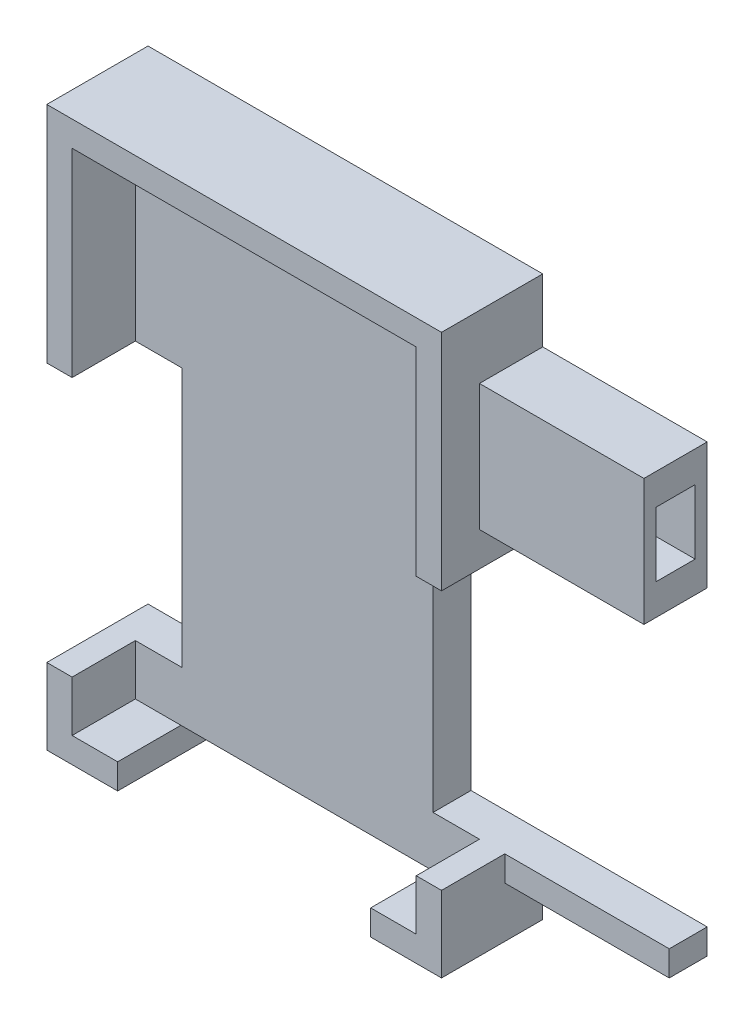
SolidWorks part; units mm, degrees
ref_plane "Front Plane" through (0, 0, 0) normal (0, 0, 1) x (1, 0, 0)
ref_plane "Top Plane" through (0, 0, 0) normal (0, 1, 0) x (1, 0, 0)
ref_plane "Right Plane" through (0, 0, 0) normal (1, 0, 0) x (0, 0, -1)
sketch "Sketch1" plane through (0, 0, 0) normal (0, 0, 1) x (1, 0, 0)
  line L0 (0, 125.6426) -> (0, -121.4419) construction
  line L1 (115.8733, 0) -> (-115.4548, 0) construction
  line L2 (15.6, 17.1) -> (28.6, 17.1)
  line L3 (-13.6, 20.1) -> (13.6, 20.1)
  line L4 (-13.6, 20.1) -> (-13.6, -20.1)
  line L5 (-13.6, -20.1) -> (13.6, -20.1)
  line L6 (13.6, 20.1) -> (13.6, -20.1)
  line L7 (-15.6, 22.1) -> (15.6, 22.1)
  line L8 (-15.6, 22.1) -> (-15.6, -22.1)
  line L9 (-15.6, -22.1) -> (15.6, -22.1)
  line L10 (15.6, 22.1) -> (15.6, -22.1)
  line L11 (28.6, 17.1) -> (28.6, 7.1)
  line L12 (28.6, 7.1) -> (15.6, 7.1)
  line L13 (11.43, 34.3394) -> (11.43, -39.7508) construction
  line L18 (-11.43, 31.8587) -> (-11.43, -35.1753) construction
  line L19 (-35.462, -16.1) -> (38.077, -16.1) construction
  line L20 (-9.93, -16.1) -> (-20.8868, -16.1)
  line L21 (9.93, 4.4) -> (20.8868, 4.4)
  line L22 (9.93, 4.4) -> (9.93, -16.1)
  line L23 (9.93, -16.1) -> (20.8868, -16.1)
  line L24 (20.8868, 4.4) -> (20.8868, -16.1)
  line L25 (-20.8868, 4.4) -> (-20.8868, -16.1)
  line L26 (-9.93, 4.4) -> (-20.8868, 4.4)
  line L27 (-9.93, 4.4) -> (-9.93, -16.1)
  line L28 (-10, -20.1) -> (-10, -22.1)
  line L29 (10, -20.1) -> (10, -22.1)
  line L30 (-35.1462, 12.1) -> (46.8082, 12.1) construction
  dimension "D1" = 31.2
  dimension "D2" = 2
  dimension "D3" = 27.2
  dimension "D4" = 40.2
  dimension "D5" = 22.86
  dimension "D6" = 4
  dimension "D7" = 1.5
  dimension "D8" = 20.5
  dimension "D9" = 10
  dimension "D10" = 10
  dimension "D11" = 5
  dimension "D12" = 13
  dimension "D13" = 28.6
  dimension "D14" = 28.2
extrude "Boss-Extrude1" add sketch "Sketch1" along normal blind 3 contours L26 L27 L20 L4 L5 L6 L23 L22 L21 L3 region at (0, 0.9335, 0)
extrude "Boss-Extrude2" add sketch "Sketch1<3>" along normal blind 5 contours L26 L4 L3 L6 L21 L10 L7 L8 | L5 L29 L9 L10 L23 L6 | L28 L5 L4 L20 L8 L9 region at (15.2413, 12.1, 0) region at (15.5179, -19.1, 0) region at (-14.6, -16.1821, 0)
sketch "Sketch1<3>" plane through (0, 0, 0) normal (0, 0, 1) x (1, 0, 0) same geometry as "Sketch1"
extrude "Boss-Extrude3" add sketch "Sketch1<4>" along normal blind 5 contours L12 L11 L2 L10 region at (22.1, 12.1, 0)
sketch "Sketch1<4>" plane through (0, 0, 0) normal (0, 0, 1) x (1, 0, 0) same geometry as "Sketch1"
sketch "Sketch2" plane through (28.6, 0, 0) normal (1, 0, 0) x (0, 0, -1)
  line L0 (0, 29.5595) -> (0, -33.1158) construction
  line L1 (-8.6556, 17.1) -> (3.1924, 17.1) construction
  line L2 (-5, 17.1) -> (0, 17.1) construction
  line L3 (-9.4008, 7.1) -> (5.047, 7.1) construction
  line L4 (-5, 7.1) -> (0, 7.1) construction
  line L5 (-2.5, 17.4146) -> (-2.5, 3.5219) construction
  line L6 (-7.7956, 12.1) -> (3.8426, 12.1) construction
  line L8 (-4.05, 14.65) -> (-0.95, 14.65)
  line L9 (-4.05, 14.65) -> (-4.05, 9.55)
  line L10 (-4.05, 9.55) -> (-0.95, 9.55)
  line L11 (-0.95, 14.65) -> (-0.95, 9.55)
  dimension "D1" = 2.5
  dimension "D2" = 5
  dimension "D3" = 5
  dimension "D4" = 3.1
  dimension "D5" = 5.1
extrude "Cut-Extrude1" cut sketch "Sketch2" against normal blind 6 contours L9 L8 L11 L10
extrude "Boss-Extrude4" add sketch "Sketch1<5>" along normal blind 8 contours L26 L4 L3 L6 L21 L10 L7 L8 | L28 L5 L4 L20 L8 L9 | L5 L29 L9 L10 L23 L6 region at (15.2413, 12.1, 0) region at (15.5179, -19.1, 0) region at (-14.6, -16.1821, 0)
sketch "Sketch1<5>" plane through (0, 0, 0) normal (0, 0, 1) x (1, 0, 0) same geometry as "Sketch1"
sketch "Sketch3" plane through (0, 0, 0) normal (0, 0, -1) x (-1, 0, 0)
  line L0 (-28.6, 7.1) -> (-15.6, 7.1) construction
  line L1 (-15.6, -16.1) -> (-28.6, -16.1)
  line L2 (-15.6, -16.1) -> (-15.6, -18.1)
  line L3 (-15.6, -18.1) -> (-28.6, -18.1)
  line L4 (-28.6, -16.1) -> (-28.6, -18.1)
  dimension "D1" = 2
extrude "Boss-Extrude5" add sketch "Sketch3" against normal blind 3
